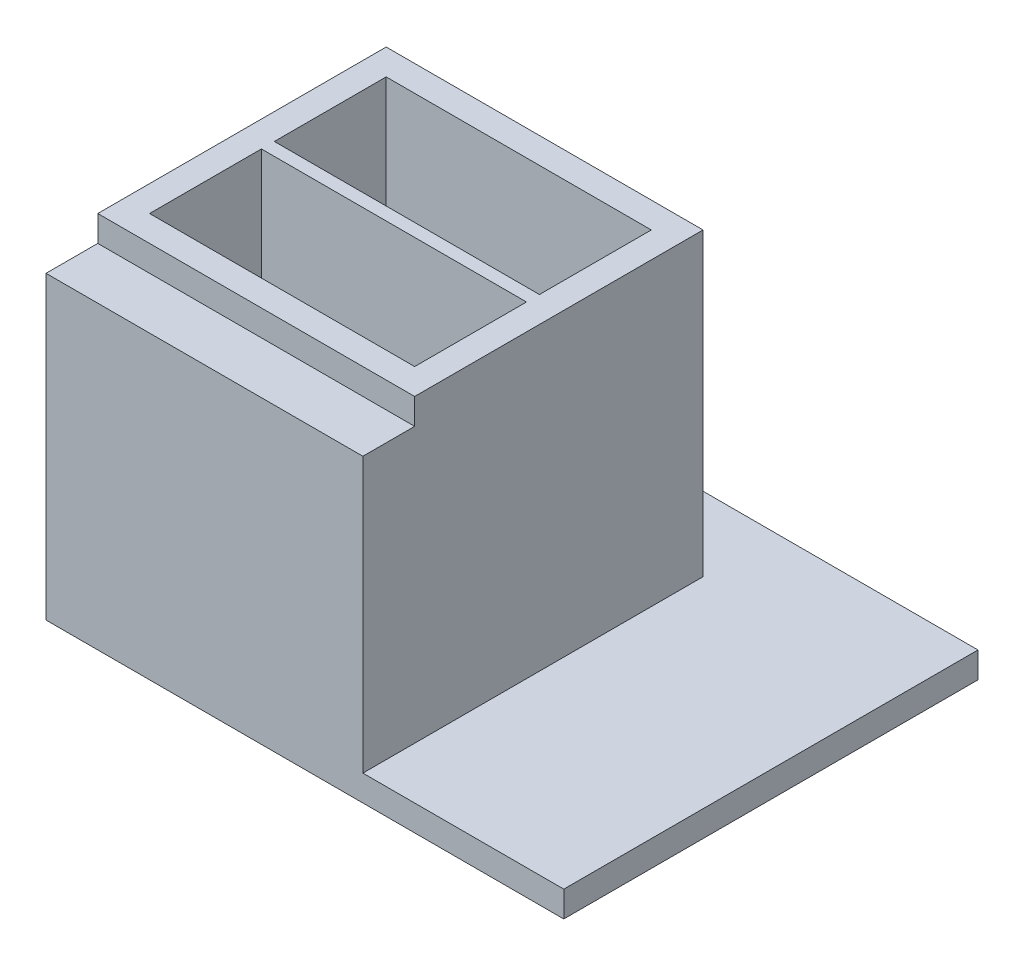
SolidWorks part; units mm, degrees
material "ABS"
ref_plane "Front Plane" through (0, 0, 0) normal (0, 0, 1) x (1, 0, 0)
ref_plane "Top Plane" through (0, 0, 0) normal (0, 1, 0) x (1, 0, 0)
ref_plane "Right Plane" through (0, 0, 0) normal (1, 0, 0) x (0, 0, -1)
sketch "Sketch1" plane through (0, 0, 0) normal (0, 1, 0) x (1, 0, 0)
  line L0 (3.175, 18.4785) -> (3.175, 32.1945)
  line L1 (0, 0) -> (63.5, 0)
  line L2 (0, 0) -> (0, 44.45)
  line L3 (0, 44.45) -> (63.5, 44.45)
  line L4 (63.5, 0) -> (63.5, 44.45)
  line L5 (4.445, 4.445) -> (34.417, 4.445)
  line L6 (4.445, 4.445) -> (4.445, 15.621)
  line L7 (4.445, 15.621) -> (34.417, 15.621)
  line L8 (34.417, 4.445) -> (34.417, 15.621)
  line L9 (4.445, 19.7485) -> (34.417, 19.7485)
  line L10 (4.445, 19.7485) -> (4.445, 30.9245)
  line L11 (4.445, 30.9245) -> (34.417, 30.9245)
  line L12 (34.417, 19.7485) -> (34.417, 30.9245)
  line L13 (3.175, 32.1945) -> (35.687, 32.1945)
  line L14 (35.687, 18.4785) -> (35.687, 32.1945)
  line L15 (3.175, 18.4785) -> (35.687, 18.4785)
  line L16 (3.175, 3.175) -> (35.687, 3.175)
  line L17 (35.687, 3.175) -> (35.687, 16.891)
  line L18 (3.175, 16.891) -> (35.687, 16.891)
  line L19 (3.175, 3.175) -> (3.175, 16.891)
  dimension "D1" = 44.45
  dimension "D2" = 63.5
  dimension "D3" = 11.176
  dimension "D4" = 29.972
  dimension "D5" = 11.176
  dimension "D6" = 29.972
  dimension "D9" = 1.5875
  dimension "D10" = 3.175
  dimension "D11" = 3.175
  dimension "D7" = 1.27
  dimension "D8" = 1.27
extrude "Boss-Extrude1" add sketch "Sketch1" along normal blind 40.005 contours L16 L19 L18 L17 L1 L4 L3 L2 L15 L0 L13 L14 region at (37.4406, 0, -24.3223)
sketch "Sketch2" plane through (0, 0, 0) normal (0, -1, 0) x (1, 0, 0)
  line L0 (3.175, -32.1945) -> (35.687, -32.1945) construction
  line L1 (3.175, -18.4785) -> (3.175, -32.1945) construction
  line L2 (3.175, -18.4785) -> (35.687, -18.4785) construction
  line L3 (35.687, -18.4785) -> (35.687, -32.1945) construction
  line L4 (0, 0) -> (0, -44.45)
  line L5 (0, -44.45) -> (63.5, -44.45)
  line L6 (63.5, -44.45) -> (63.5, 0)
  line L7 (63.5, 0) -> (0, 0)
  line L8 (0, 0) -> (0, -44.45)
  line L9 (0, -44.45) -> (63.5, -44.45)
  line L10 (63.5, -44.45) -> (63.5, 0)
  line L11 (63.5, 0) -> (0, 0)
  line L12 (35.687, -3.175) -> (35.687, -16.891) construction
  line L13 (3.175, -3.175) -> (35.687, -3.175) construction
  line L14 (3.175, -3.175) -> (3.175, -16.891) construction
  line L15 (3.175, -16.891) -> (35.687, -16.891) construction
  line L16 (3.175, -32.1945) -> (35.687, -32.1945)
  line L17 (3.175, -18.4785) -> (3.175, -32.1945)
  line L18 (3.175, -18.4785) -> (35.687, -18.4785)
  line L19 (35.687, -18.4785) -> (35.687, -32.1945)
  line L20 (35.687, -3.175) -> (35.687, -16.891)
  line L21 (3.175, -3.175) -> (35.687, -3.175)
  line L22 (3.175, -3.175) -> (3.175, -16.891)
  line L23 (3.175, -16.891) -> (35.687, -16.891)
  line M9 (3.175, -18.4785) -> (35.687, -18.4785)
  line M10 (35.687, -18.4785) -> (35.687, -32.1945)
  line M11 (35.687, -32.1945) -> (3.175, -32.1945)
  line M12 (3.175, -32.1945) -> (3.175, -18.4785)
  line M13 (3.175, -3.175) -> (35.687, -3.175)
  line M14 (35.687, -3.175) -> (35.687, -16.891)
  line M15 (35.687, -16.891) -> (3.175, -16.891)
  line M16 (3.175, -16.891) -> (3.175, -3.175)
  dimension "D1" = 0
extrude "Boss-Extrude2" add sketch "Sketch2" against normal blind 2.54 contours M13 M16 M15 M14 | M9 M12 M11 M10 region at (19.431, 0, -25.3365) region at (19.431, 0, -10.033)
sketch "Sketch3" plane through (0, 40.005, 0) normal (0, 1, 0) x (1, 0, 0)
  line L33 (35.687, 35.3695) -> (3.175, 35.3695)
  line L34 (35.687, 35.3695) -> (3.175, 35.3695)
  line L36 (0, 32.1945) -> (0, 18.4785)
  line L37 (0, 32.1945) -> (0, 18.4785)
  line L38 (0, 0) -> (63.5, 0) construction
  line L39 (38.862, 18.4785) -> (38.862, 32.1945)
  line L40 (38.862, 18.4785) -> (38.862, 32.1945)
  line L41 (0, 35.3695) -> (38.862, 35.3695)
  line L42 (0, 35.3695) -> (0, 0)
  line L43 (0, 0) -> (38.862, 0)
  line L44 (38.862, 35.3695) -> (38.862, 0)
  line L49 (0, 44.45) -> (0, 0)
  line L50 (0, 0) -> (63.5, 0)
  line L51 (63.5, 0) -> (63.5, 44.45)
  line L52 (63.5, 44.45) -> (0, 44.45)
  line L53 (0, 44.45) -> (0, 0)
  line L54 (0, 0) -> (63.5, 0)
  line L55 (63.5, 0) -> (63.5, 44.45)
  line L56 (63.5, 44.45) -> (0, 44.45)
  line M11 (0, 44.45) -> (0, 0)
  line M12 (0, 0) -> (63.5, 0)
  line M13 (63.5, 0) -> (63.5, 44.45)
  line M14 (63.5, 44.45) -> (0, 44.45)
  dimension "D4" = 0
  dimension "D1" = 3.175
  dimension "D2" = 3.175
  dimension "D3" = 3.175
extrude "Cut-Extrude1" cut sketch "Sketch3" against normal blind 36.83 contours L41 L44 L40 L42 L37 L34 M12 M13 M14 M11 region at (43.4436, 40.005, -26.5347)
sketch "Sketch9" plane through (0, 0, 0) normal (0, 0, 1) x (1, 0, 0)
  line L0 (38.862, 3.175) -> (38.862, 40.005) construction
  line L1 (0, 40.005) -> (38.862, 40.005)
  line L2 (0, 40.005) -> (0, 36.83)
  line L3 (0, 36.83) -> (38.862, 36.83)
  line L4 (38.862, 40.005) -> (38.862, 36.83)
  line L11 (63.5, 3.175) -> (38.862, 3.175)
  line L12 (38.862, 3.175) -> (38.862, 40.005)
  line L13 (38.862, 40.005) -> (0, 40.005)
  line L14 (0, 40.005) -> (0, 0)
  line L15 (0, 0) -> (63.5, 0)
  line L16 (63.5, 0) -> (63.5, 3.175)
  line L18 (38.862, 3.175) -> (38.862, 40.005)
  line L19 (38.862, 40.005) -> (0, 40.005)
  line L20 (0, 40.005) -> (0, 0)
  line L21 (0, 0) -> (63.5, 0)
  line L22 (63.5, 0) -> (63.5, 3.175)
  line L23 (63.5, 3.175) -> (38.862, 3.175)
  line M12 (38.862, 3.175) -> (38.862, 40.005)
  line M14 (0, 40.005) -> (0, 0)
  line M15 (0, 0) -> (63.5, 0)
  line M16 (63.5, 0) -> (63.5, 3.175)
  dimension "D1" = 3.175
  dimension "D2" = 0
extrude "Boss-Extrude8" add sketch "Sketch9" along normal blind 6.35 contours L3 M14 M15 M16 M12 region at (21.0763, 17.543, 0)
